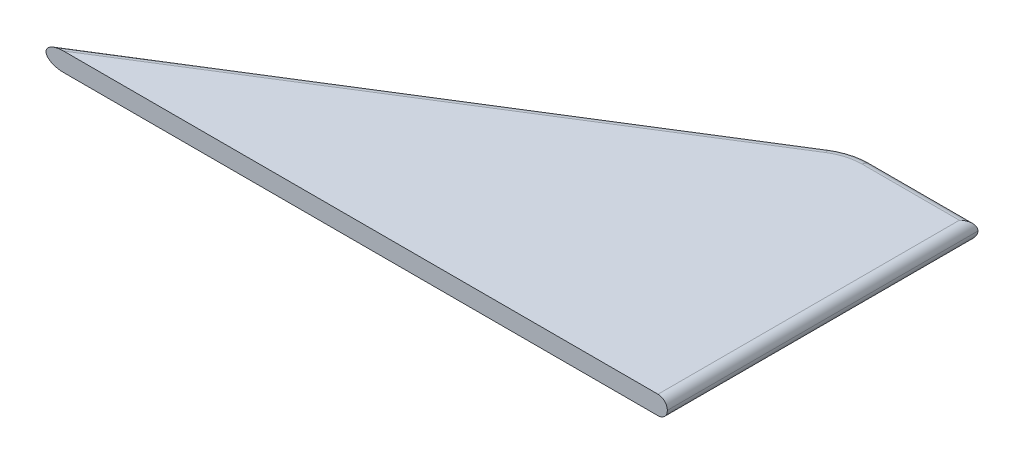
SolidWorks part; units mm, degrees
ref_plane "Front Plane" through (0, 0, 0) normal (0, 0, 1) x (1, 0, 0)
ref_plane "Top Plane" through (0, 0, 0) normal (0, 1, 0) x (1, 0, 0)
ref_plane "Right Plane" through (0, 0, 0) normal (1, 0, 0) x (0, 0, -1)
sketch "Sketch1" plane through (0, 0, 0) normal (0, 1, 0) x (1, 0, 0)
  line L0 (0, 0) -> (100, 0)
  line L1 (100, 0) -> (100, 50)
  line L2 (100, 50) -> (80, 50)
  line L3 (80, 50) -> (0, 0)
  dimension "D1" = 100
  dimension "D2" = 50
  dimension "D3" = 20
extrude "Boss-Extrude1" add sketch "Sketch1" along normal blind 3
fillet "Fillet1" radius 10 1 edges at (80, 1.5, -50)
fillet "Fillet2" radius 1.5 8 edges at (91.434, 0, -50) (80.1111, 0, -49.6125) (91.434, 3, -50) (80.1111, 3, -49.6125) (100, 3, -25) (100, 0, -25) (38.784, 0, -24.24) (38.784, 3, -24.24)
